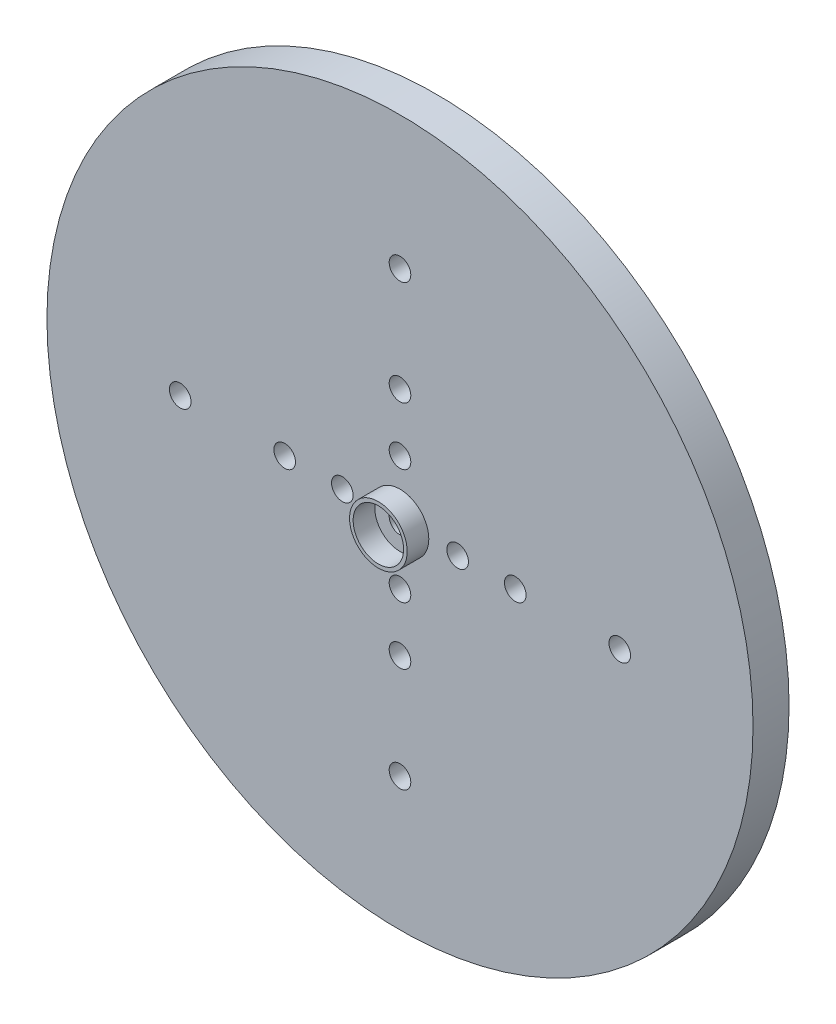
SolidWorks part; units mm, degrees
material "Nylon 101"
ref_plane "Front Plane" through (0, 0, 0) normal (0, 0, 1) x (1, 0, 0)
ref_plane "Top Plane" through (0, 0, 0) normal (0, 1, 0) x (1, 0, 0)
ref_plane "Right Plane" through (0, 0, 0) normal (1, 0, 0) x (0, 0, -1)
sketch "Sketch1" plane through (0, 0, 0) normal (0, 0, 1) x (1, 0, 0)
  circle A0 centre (-26.6506, 0) radius 49
extrude "Boss-Extrude1" add sketch "Sketch1" along normal blind 5 contours A0
sketch "Sketch2" plane through (0, 0, 0) normal (0, 0, -1) x (-1, 0, 0)
  circle A0 centre (26.6506, 0) radius 3
  circle A1 centre (26.6506, 0) radius 4.5
  dimension "D2" = 9
  dimension "D3" = 6
extrude "Boss-Extrude2" add sketch "Sketch2" against normal blind 4
extrude "Boss-Extrude3" add sketch "Sketch2<2>" along normal blind 4
sketch "Sketch2<2>" plane through (0, 0, 0) normal (0, 0, -1) x (-1, 0, 0) same geometry as "Sketch2"
sketch "Sketch3" plane through (0, 0, 5) normal (0, 0, 1) x (1, 0, 0)
  circle A0 centre (-26.6506, 0) radius 4
  circle A1 centre (-26.6506, 0) radius 3.5
  dimension "D2" = 8
  dimension "D3" = 7
extrude "Boss-Extrude4" add sketch "Sketch3" along normal blind 3
sketch "Sketch4" plane through (0, 0, 5) normal (0, 0, 1) x (1, 0, 0)
  circle A0 centre (-26.6506, 0) radius 1.5
  dimension "D1" = 3
extrude "Cut-Extrude1" cut sketch "Sketch4" against normal blind 5
sketch "Sketch5" plane through (0, 0, 5) normal (0, 0, 1) x (1, 0, 0)
  circle A1 centre (-34.6506, 0) radius 1.5
  circle A2 centre (-42.6506, 0) radius 1.5
  circle A3 centre (-57.1506, 0) radius 1.5
  circle A4 centre (-26.6506, 8) radius 1.5
  circle A5 centre (-26.6506, 16) radius 1.5
  circle A6 centre (-26.6506, 30.5) radius 1.5
  circle A7 centre (-18.6506, 0) radius 1.5
  circle A8 centre (-10.6506, 0) radius 1.5
  circle A9 centre (3.8494, 0) radius 1.5
  circle A10 centre (-26.6506, -8) radius 1.5
  circle A11 centre (-26.6506, -16) radius 1.5
  circle A12 centre (-26.6506, -30.5) radius 1.5
  point P29 (-26.6506, 0)
  dimension "D1" = 4
extrude "Cut-Extrude2" cut sketch "Sketch5" against normal blind 5
